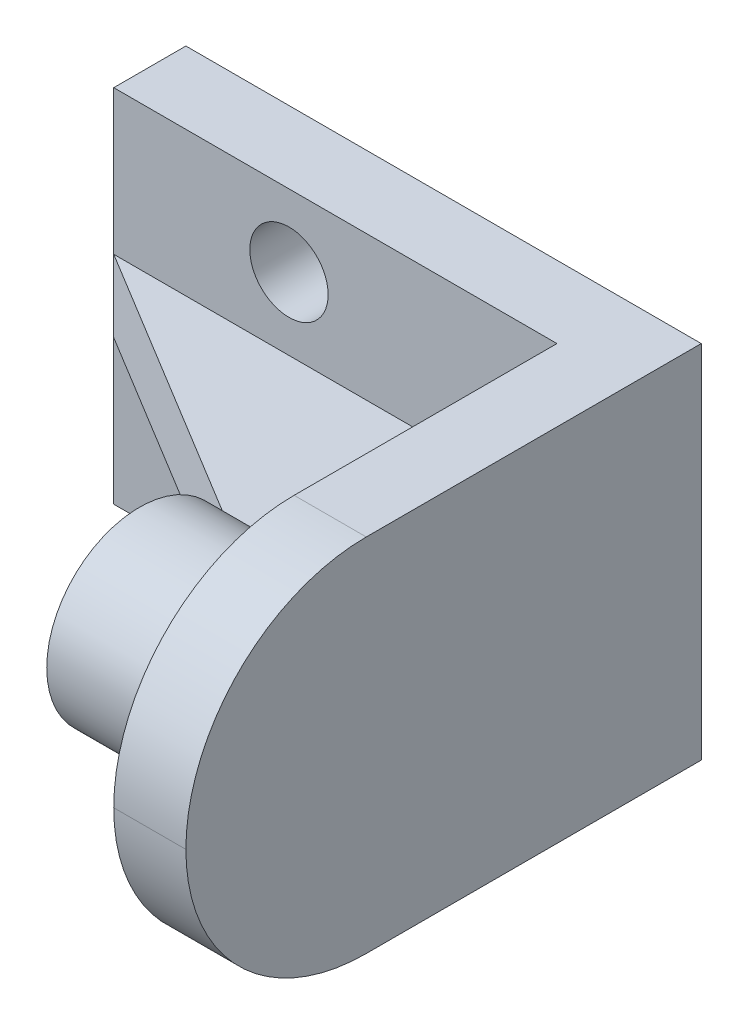
SolidWorks part; units mm, degrees
ref_plane "Спереди" through (0, 0, 0) normal (0, 0, 1) x (1, 0, 0)
ref_plane "Сверху" through (0, 0, 0) normal (0, 1, 0) x (1, 0, 0)
ref_plane "Справа" through (0, 0, 0) normal (1, 0, 0) x (0, 0, -1)
sketch "Эскиз1" plane through (0, 0, 0) normal (0, 0, 1) x (1, 0, 0)
  line L1 (50, 35) -> (-50, 35)
  line L2 (50, 35) -> (50, -35)
  line L3 (50, -35) -> (-50, -35)
  line L4 (-50, 35) -> (-50, -35)
  line L5 (50, 35) -> (-50, -35) construction
  line L6 (50, -35) -> (-50, 35) construction
  point P0 (0, 0)
  dimension "D1" = 100
  dimension "D2" = 70
extrude "Бобышка-Вытянуть1" add sketch "Эскиз1" along normal blind 14
sketch "Эскиз2" plane through (0, 0, 14) normal (0, 0, 1) x (1, 0, 0)
sketch "Эскиз4" plane through (0, 0, 14) normal (0, 0, 1) x (1, 0, 0)
  line L0 (-50, -35) -> (50, -35) construction
  line L1 (50, 35) -> (36, 35)
  line L2 (50, 35) -> (50, -35)
  line L3 (50, -35) -> (36, -35)
  line L4 (36, 35) -> (36, -35)
  dimension "D1" = 14
extrude "Бобышка-Вытянуть2" add sketch "Эскиз4" along normal blind 86
fillet "Скругление1" radius 35 1 edges at (43, 35, 100)
fillet "Скругление2" radius 35 1 edges at (43, -35, 100)
sketch "Эскиз5" plane through (0, 0, 14) normal (0, 0, 1) x (1, 0, 0)
  circle A0 centre (-16, 21) radius 7.6
extrude "Вырез-Вытянуть1" cut sketch "Эскиз5" against normal through all
sketch "Эскиз6" plane through (0, 0, 14) normal (0, 0, 1) x (1, 0, 0)
  circle A0 centre (-16, -21) radius 7.6
extrude "Вырез-Вытянуть2" cut sketch "Эскиз6" against normal through all
sketch "Эскиз7" plane through (36, 0, 0) normal (-1, 0, 0) x (0, 0, 1)
  line L0 (100, 0) -> (65, 0)
  circle A0 centre (65, 0) radius 18
  circle A1 centre (65, 0) radius 10
extrude "Бобышка-Вытянуть3" add sketch "Эскиз7" along normal blind 30 contours A1 A0 region at (36, 0, 47.5091)
sketch "Эскиз8" plane through (0, 0, 14) normal (0, 0, 1) x (1, 0, 0)
  line L0 (-50, 35) -> (-50, -35) construction
  line L1 (50, 7) -> (-50, 7)
  line L2 (50, 7) -> (50, -7)
  line L3 (50, -7) -> (-50, -7)
  line L4 (-50, 7) -> (-50, -7)
  line L5 (50, 7) -> (-50, -7) construction
  line L6 (50, -7) -> (-50, 7) construction
  point P0 (0, 0)
  dimension "D1" = 14
extrude "Бобышка-Вытянуть4" add sketch "Эскиз8" along normal blind 34
sketch "Эскиз9" plane through (0, -7, 0) normal (0, -1, 0) x (-1, 0, 0)
  line L0 (-6, -48) -> (50, -14)
split "Разделить1" trim tools "Эскиз9" bodies to split 108 resulting bodies 109
